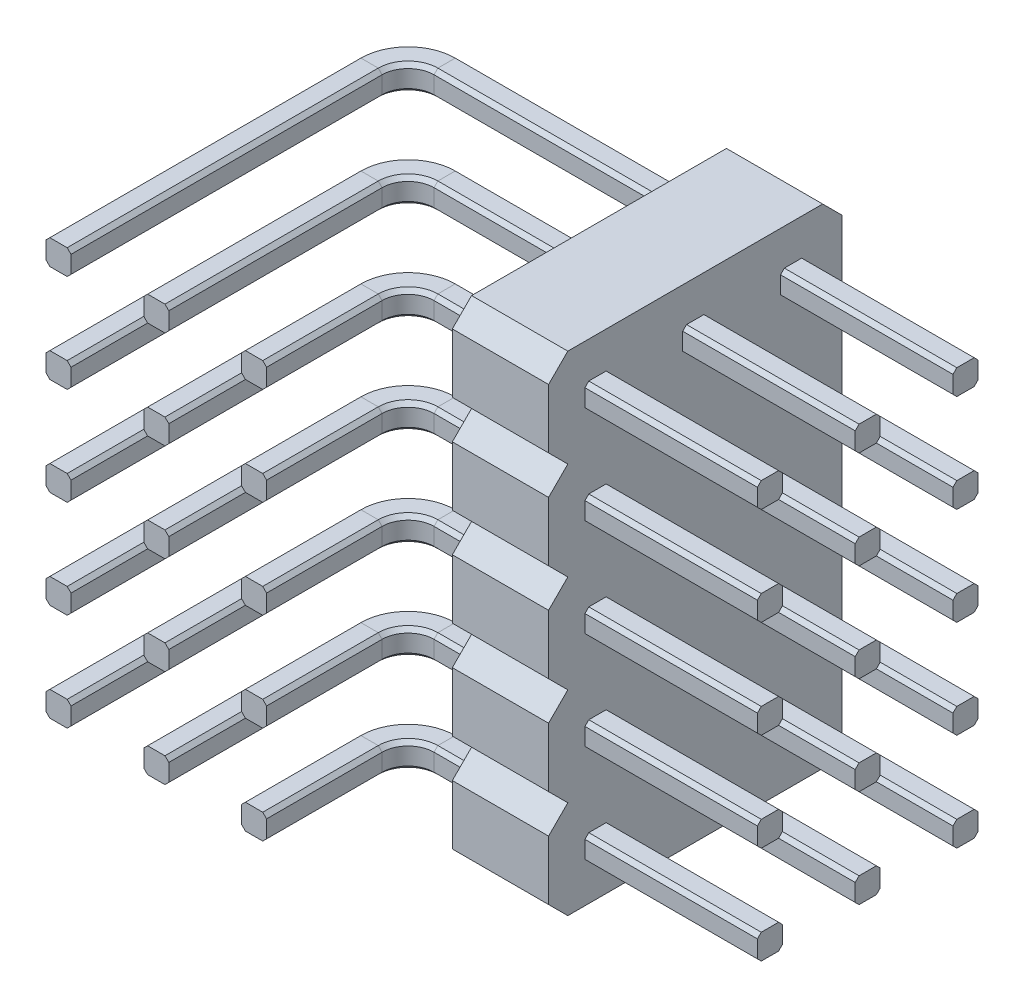
SolidWorks part; units mm, degrees
ref_plane "Front Plane" through (0, 0, 0) normal (0, 0, 1) x (1, 0, 0)
ref_plane "Top Plane" through (0, 0, 0) normal (0, 1, 0) x (1, 0, 0)
ref_plane "Right Plane" through (0, 0, 0) normal (1, 0, 0) x (0, 0, -1)
sketch "Sketch1" plane through (0, 0, 0) normal (0, 0, 1) x (1, 0, 0)
  line L0 (-0.325, 0.225) -> (-0.225, 0.325)
  line L1 (-0.225, -0.325) -> (0.225, -0.325)
  line L2 (-0.325, -0.225) -> (-0.325, 0.225)
  line L3 (-0.225, 0.325) -> (0.225, 0.325)
  line L4 (0.325, -0.225) -> (0.325, 0.225)
  line L5 (-0.325, -0.325) -> (0.325, 0.325) construction
  line L6 (-0.325, 0.325) -> (0.325, -0.325) construction
  line L7 (0.225, 0.325) -> (0.325, 0.225)
  line L8 (0.225, -0.325) -> (0.325, -0.225)
  line L9 (-0.325, -0.225) -> (-0.225, -0.325)
  line L10 (2.315, -0.325) -> (2.765, -0.325)
  line L11 (2.215, -0.225) -> (2.315, -0.325)
  line L12 (2.215, -0.225) -> (2.215, 0.225)
  line L13 (2.215, 0.225) -> (2.315, 0.325)
  line L14 (2.315, 0.325) -> (2.765, 0.325)
  line L15 (2.765, 0.325) -> (2.865, 0.225)
  line L16 (2.865, -0.225) -> (2.865, 0.225)
  line L17 (2.765, -0.325) -> (2.865, -0.225)
  line L18 (4.855, -0.325) -> (5.305, -0.325)
  line L19 (4.755, -0.225) -> (4.855, -0.325)
  line L20 (4.755, -0.225) -> (4.755, 0.225)
  line L21 (4.755, 0.225) -> (4.855, 0.325)
  line L22 (4.855, 0.325) -> (5.305, 0.325)
  line L23 (5.305, 0.325) -> (5.405, 0.225)
  line L24 (5.405, -0.225) -> (5.405, 0.225)
  line L25 (5.305, -0.325) -> (5.405, -0.225)
  point P0 (0, 0)
  dimension "D1" = 0.65
  dimension "D2" = 3
sketch "Sketch2" plane through (0, 0, 0) normal (0, 1, 0) x (1, 0, 0)
  line L0 (0, 0) -> (0, 8.08)
  line L1 (1, 9.08) -> (14.48, 9.08)
  line L2 (2.54, 0) -> (2.54, 5.54)
  line L3 (2.315, 0) -> (2.765, 0) construction
  line L4 (3.54, 6.54) -> (14.48, 6.54)
  line L5 (5.08, 0) -> (5.08, 3)
  line L6 (4.855, 0) -> (5.305, 0) construction
  line L7 (6.08, 4) -> (14.48, 4)
  arc A0 (5.08, 3) -> (6.08, 4) centre (6.08, 3) cw
  arc A1 (2.54, 5.54) -> (3.54, 6.54) centre (3.54, 5.54) cw
  arc A2 (0, 8.08) -> (1, 9.08) centre (1, 8.08) cw
  point P14 (0, 0)
  point P17 (5.08, 4)
  point P20 (2.54, 6.54)
  point P23 (0, 9.08)
  dimension "D5" = 1
  dimension "D1" = 9.08
  dimension "D2" = 14.48
  dimension "D3" = 6.54
  dimension "D4" = 4
sweep "Sweep2" add profiles "Sketch1" path "Sketch2"
sweep "Sweep3" add profiles "Sketch1<3>" path "Sketch2<3>"
sketch "Sketch1<3>" plane through (0, 0, 0) normal (0, 0, 1) x (1, 0, 0) same geometry as "Sketch1"
sketch "Sketch2<3>" plane through (0, 0, 0) normal (0, 1, 0) x (1, 0, 0) same geometry as "Sketch2"
sweep "Sweep4" add profiles "Sketch1<4>" path "Sketch2<4>"
sketch "Sketch1<4>" plane through (0, 0, 0) normal (0, 0, 1) x (1, 0, 0) same geometry as "Sketch1"
sketch "Sketch2<4>" plane through (0, 0, 0) normal (0, 1, 0) x (1, 0, 0) same geometry as "Sketch2"
ref_plane "Plane1" through (7.5, 0, 0) normal (1, 0, 0) x (0, 0, -1)
sketch "Sketch3" plane through (7.5, 0, 0) normal (1, 0, 0) x (0, 0, -1)
  line L0 (9.405, 0) -> (3.675, 0) construction
  line L1 (9.405, 0.225) -> (9.405, -0.225) construction
  line L2 (0, 0) -> (8.08, 0) construction
  line L3 (3.675, -0.225) -> (3.675, 0.225) construction
  line L4 (9.08, -0.325) -> (9.08, 0.325) construction
  line L5 (3.23, 1.27) -> (9.85, 1.27)
  line L6 (2.73, 0.77) -> (2.73, -0.77)
  line L7 (3.23, -1.27) -> (9.85, -1.27)
  line L8 (10.35, 0.77) -> (10.35, -0.77)
  line L9 (2.73, 1.27) -> (10.35, -1.27) construction
  line L10 (2.73, -1.27) -> (10.35, 1.27) construction
  line L11 (9.305, -0.325) -> (8.855, -0.325) construction
  line L12 (8.855, 0.325) -> (9.305, 0.325) construction
  line L13 (2.73, 0.77) -> (3.23, 1.27)
  line L14 (2.73, -0.77) -> (3.23, -1.27)
  line L15 (9.85, -1.27) -> (10.35, -0.77)
  line L16 (9.85, 1.27) -> (10.35, 0.77)
  point P5 (6.54, 0)
  point P21 (9.08, -0.325)
  dimension "D1" = 7.62
  dimension "D2" = 2.54
extrude "Boss-Extrude1" add sketch "Sketch3" along normal blind 2.5
pattern_linear "LPattern1" count 5 spacing 2.54 along (0, -1, 0) of bodies 104
combine bodies "Combine1" operation type add bodies to combine 105 104 106 107 108
